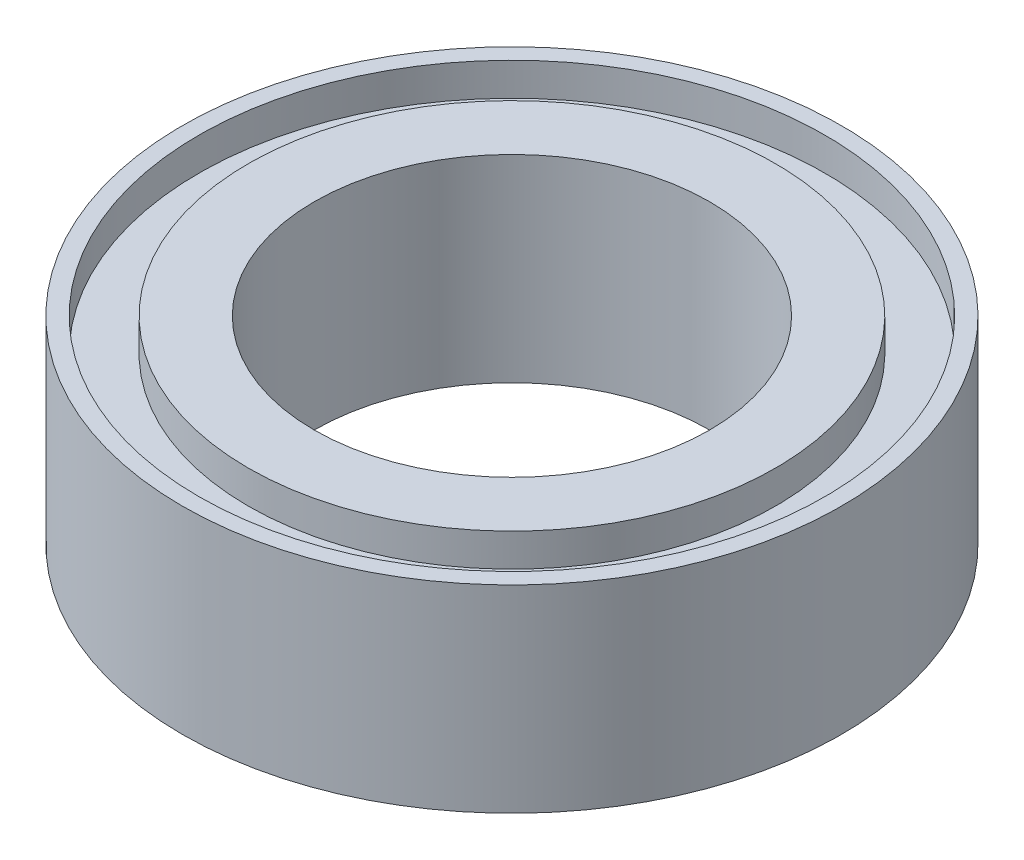
SolidWorks part; units mm, degrees
ref_plane "前视基准面" through (0, 0, 0) normal (0, 0, 1) x (1, 0, 0)
ref_plane "上视基准面" through (0, 0, 0) normal (0, 1, 0) x (1, 0, 0)
ref_plane "右视基准面" through (0, 0, 0) normal (1, 0, 0) x (0, 0, -1)
sketch "草图1" plane through (0, 0, 0) normal (0, 1, 0) x (1, 0, 0)
  line L0 (-16.6561, 0) -> (16.6561, 0) construction
  line L1 (0, 15.7031) -> (0, -15.7031) construction
  circle A0 centre (0, 0) radius 5
  circle A1 centre (0, 0) radius 3
  circle A2 centre (0, 0) radius 4.75
  circle A3 centre (0, 0) radius 4
  point P4 (0, 0)
  point P8 (0, 0)
  dimension "D1" = 10
  dimension "D2" = 6
  dimension "D3" = 9.5
  dimension "D4" = 8
extrude "凸台-拉伸1" add sketch "草图1" along normal mid plane 3 contours A0 A2 | A3 A1 region at (-4.8586, 0, 0) region at (-3.8869, 0, 0)
extrude "凸台-拉伸2" add sketch "草图1<3>" along normal mid plane 2 contours A2 A3 region at (-4.6156, 0, 0)
sketch "草图1<3>" plane through (0, 0, 0) normal (0, 1, 0) x (1, 0, 0) same geometry as "草图1"
